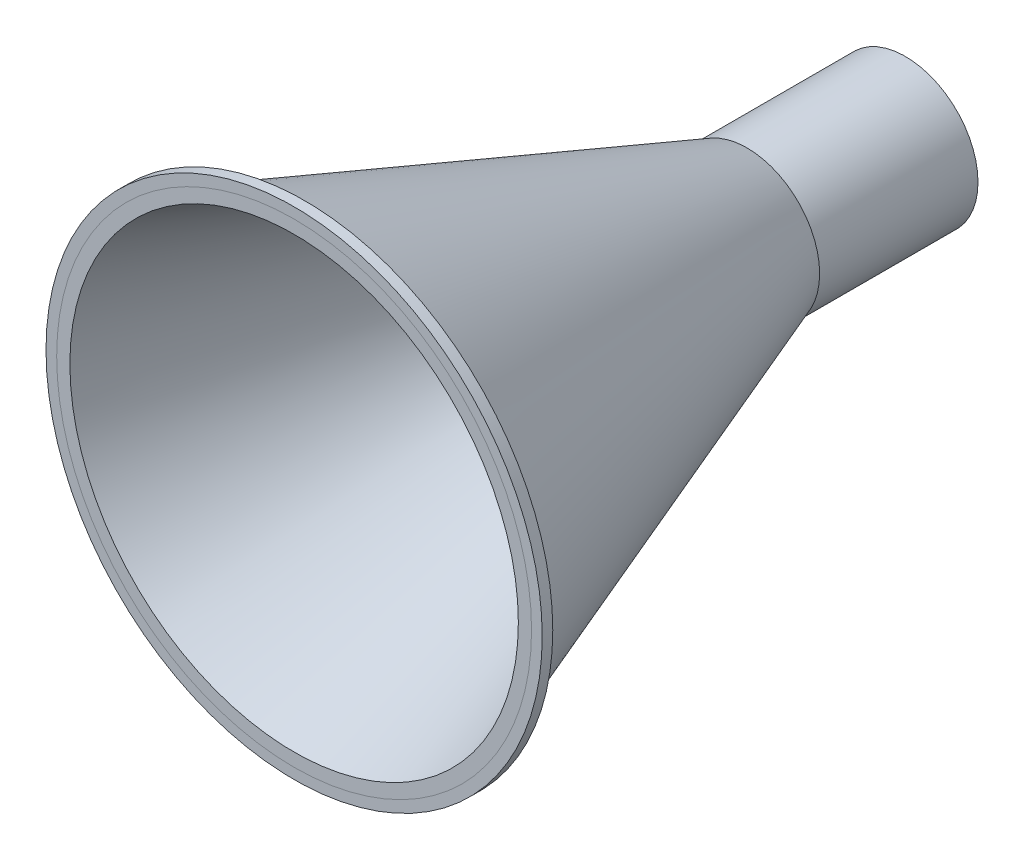
SolidWorks part; units mm, degrees
ref_plane "Front Plane" through (0, 0, 0) normal (0, 0, 1) x (1, 0, 0)
ref_plane "Top Plane" through (0, 0, 0) normal (0, 1, 0) x (1, 0, 0)
ref_plane "Right Plane" through (0, 0, 0) normal (1, 0, 0) x (0, 0, -1)
sketch "Sketch13" plane through (0, 0, 0) normal (0, 0, 1) x (1, 0, 0)
  circle A0 centre (0, 0) radius 17.4625
  dimension "D1" = 34.925
extrude "Boss-Extrude5" add sketch "Sketch13" along normal blind 108.966 draft 20 draft outward yes
sketch "Sketch14" plane through (0, 0, 0) normal (0, 0, -1) x (-1, 0, 0)
  circle A0 centre (0, 0) radius 14.2875
  dimension "D1" = 28.575
extrude "Cut-Extrude3" cut sketch "Sketch14" against normal blind 108.966 draft 20 draft outward yes
sketch "Sketch17" plane through (0, 0, 0) normal (0, 0, -1) x (-1, 0, 0)
  circle A0 centre (0, 0) radius 17.4625
  circle A1 centre (0, 0) radius 12.7
extrude "Boss-Extrude6" add sketch "Sketch17" along normal blind 38.1
chamfer "Chamfer2" distance 2.54 angle 45 1 edges at (-12.7, 0, -38.1)
thread "Thread1" pitch 3.5 method cut profile "Thread Profile2" start angle 0, offset 0, length 25.4, pitch 3.5, diameter 25.4
ref_plane "Plane6" through (12.7, 0, -35.56) normal (0, -1, 0) x (1, 0, 0)
sketch "Thread Profile2" plane through (12.7, 0, -35.56) normal (0, -1, 0) x (1, 0, 0)
  line L0 (0, 0) -> (0, 3.5) construction
  line L1 (0, 0) -> (1.8944, 1.0937)
  line L2 (1.8944, 1.0937) -> (1.8944, 1.5312)
  line L3 (1.8944, 1.5312) -> (0, 2.625)
  line L4 (1.8944, 1.3125) -> (0, 1.3125) construction
  line L11 (0, 0) -> (0, 2.625)
  point P2 (0, 0)
  dimension "Pitch" = 3.5
  dimension "Profile_Angle" = 60
  dimension "Profile_Land" = 0.4375
  dimension "Profile_Height" = 1.8944
sketch "Sketch26" plane through (0, 0, 108.966) normal (0, 0, 1) x (1, 0, 0)
  circle A0 centre (0, 0) radius 59.69
  circle A1 centre (0, 0) radius 57.1229
  dimension "D1" = 119.38
extrude "Boss-Extrude7" add sketch "Sketch26" against normal blind 2.54 separate body
